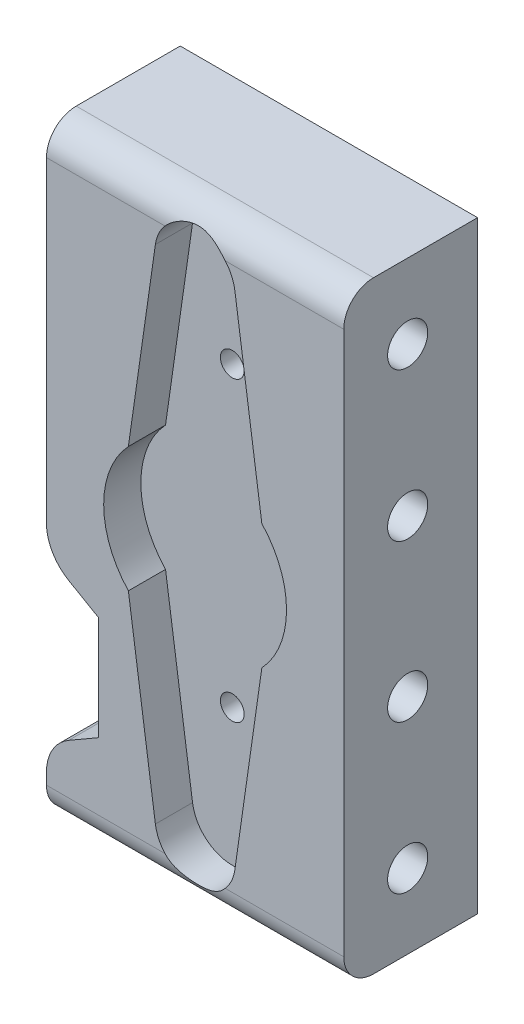
SolidWorks part; units mm, degrees
ref_plane "Front Plane" through (0, 0, 0) normal (0, 0, 1) x (1, 0, 0)
ref_plane "Top Plane" through (0, 0, 0) normal (0, 1, 0) x (1, 0, 0)
ref_plane "Right Plane" through (0, 0, 0) normal (1, 0, 0) x (0, 0, -1)
sketch "Sketch1" plane through (0, 0, 0) normal (0, 0, 1) x (1, 0, 0)
  line L0 (-10, 20.2804) -> (-10, -20.2804)
  line L1 (-10, -20.2804) -> (10, -20.2804)
  line L2 (10, -20.2804) -> (10, 20.2804)
  line L3 (10, 20.2804) -> (-10, 20.2804)
  line L4 (10, -20.2804) -> (-10, 20.2804) construction
  line L5 (10, 20.2804) -> (-10, -20.2804) construction
  point P4 (0, 0)
  dimension "D1" = 20
  dimension "D2" = 40.5608
extrude "Boss-Extrude1" add sketch "Sketch1" against normal blind 9
sketch "Sketch6" plane through (10, 0, 0) normal (1, 0, 0) x (0, 0, -1)
  line L0 (0, -20.2804) -> (0, 20.2804) construction
  line L2 (4.3, 4.95) -> (4.3, 15.6283) construction
  line L3 (0, 0) -> (9, 0) construction
  line L4 (9, -20.2804) -> (9, 20.2804) construction
  line L5 (4.3, -15.2652) -> (4.3, -5.2652) construction
  line L6 (-4.0611, -10.2652) -> (12.6611, -10.2652) construction
  line L7 (9, -20.2804) -> (0, -20.2804) construction
  line L8 (-4.0611, -0.25) -> (12.6611, -0.25) construction
  circle A0 centre (4.3, -15.2652) radius 1.35
  circle A1 centre (4.3, -5.2652) radius 1.35
  circle A2 centre (4.3, 15.2652) radius 1.35
  circle A3 centre (4.3, 5.2652) radius 1.35
  point P18 (4.3, -10.2652)
  point P22 (4.3, -10.2652)
  dimension "D1" = 2.7
  dimension "D2" = 4.7
  dimension "D3" = 10.0152
  dimension "D4" = 10
  dimension "D5" = 10.0152
extrude "Cut-Extrude1" cut sketch "Sketch6" against normal blind 10
sketch "Sketch8" plane through (0, 0, 0) normal (0, 0, 1) x (1, 0, 0)
  line L0 (-10, 20.2804) -> (10, -20.2804) construction
  line L1 (-4.489, -4.2038) -> (-2.6727, -16.8829)
  line L2 (4.3, 4.1125) -> (4.3, -4.1125) construction
  line L3 (0, -16.5) -> (0, 16.5) construction
  line L4 (2.6727, -16.8829) -> (4.489, -4.2038)
  line L5 (-4.3, 4.1125) -> (4.3, 4.1125) construction
  line L6 (-4.3, -4.1125) -> (4.3, -4.1125) construction
  line L7 (4.489, 4.2038) -> (2.6727, 16.8829)
  line L8 (-2.6727, 16.8829) -> (-4.489, 4.2038)
  line L12 (-4.3, -4.1125) -> (-2.4747, -16.8545) construction
  line L13 (2.4747, -16.8545) -> (4.3, -4.1125) construction
  line L14 (4.3, 4.1125) -> (2.4747, 16.8545) construction
  line L15 (-2.4747, 16.8545) -> (-4.3, 4.1125) construction
  arc A0 (-2.6727, -16.8829) -> (2.6727, -16.8829) centre (0, -16.5) ccw
  arc A1 (4.489, -4.2038) -> (4.489, 4.2038) centre (0, 0) ccw
  arc A2 (2.6727, 16.8829) -> (-2.6727, 16.8829) centre (0, 16.5) ccw
  arc A3 (-4.489, 4.2038) -> (-4.489, -4.2038) centre (0, 0) ccw
  arc A12 (-4.3, 4.1125) -> (-4.3, -4.1125) centre (0, 0) ccw construction
  arc A13 (-2.4747, -16.8545) -> (2.4747, -16.8545) centre (0, -16.5) ccw construction
  arc A14 (4.3, -4.1125) -> (4.3, 4.1125) centre (0, 0) ccw construction
  arc A15 (2.4747, 16.8545) -> (-2.4747, 16.8545) centre (0, 16.5) ccw construction
  point P10 (0, 0)
  dimension "D1" = 5.95
  dimension "D3" = 2.5
  dimension "D2" = 8.6
  dimension "D4" = 33
  dimension "D5" = 8.225
  dimension "D6" = 0.2
extrude "Cut-Extrude2" cut sketch "Sketch8" against normal blind 2.5
fillet "Fillet1" radius 2 2 edges at (0, -20.2804, 0) (0, 20.2804, 0) tangent propagation no
sketch "Sketch9" plane through (0, 0, -2.5) normal (0, 0, 1) x (1, 0, 0)
  line L0 (0, 20) -> (0, -49980) construction
  line L1 (-6.15, 0) -> (6.15, 0) construction
  circle A0 centre (0, 10) radius 0.8
  arc A2 (-4.489, 4.2038) -> (-4.489, -4.2038) centre (0, 0) ccw construction
  arc A3 (4.489, -4.2038) -> (4.489, 4.2038) centre (0, 0) ccw construction
  circle A4 centre (0, -10) radius 0.8
  dimension "D1" = 1.6
  dimension "D2" = 10
extrude "Cut-Extrude3" cut sketch "Sketch9" against normal up to surface (6.5 mm away) up to face at (0, 0, -9)
sketch "Sketch10" plane through (-10, 0, 0) normal (-1, 0, 0) x (0, 0, 1)
  line L0 (0, -10.2652) -> (-9, -10.2652) construction
  line L1 (0, 18.2804) -> (0, -18.2804) construction
  line L2 (-9, 20.2804) -> (-9, -20.2804) construction
  line L3 (-9, -20.2804) -> (-2, -20.2804) construction
  line L4 (0, -6.7652) -> (-9, -6.7652)
  line L5 (0, -13.7652) -> (-9, -13.7652)
  line L6 (0, -13.7652) -> (0, -6.7652)
  line L7 (-9, -6.7652) -> (-9, -13.7652)
  dimension "D1" = 10.0152
  dimension "D2" = 3.5
  dimension "D3" = 3.5
extrude "Cut-Extrude4" cut sketch "Sketch10" against normal blind 3.5
chamfer "Chamfer1" distance 3.5 angle 30 2 edges at (-10, -6.7652, -4.5) (-10, -13.7652, -4.5) first distance on face at (-8.25, -6.7652, -4.5) first distance on face at (-8.25, -13.7652, -4.5)
fillet "Fillet2" radius 3 2 edges at (-10, -4.7444, -4.5) (-10, -15.7859, -4.5)
